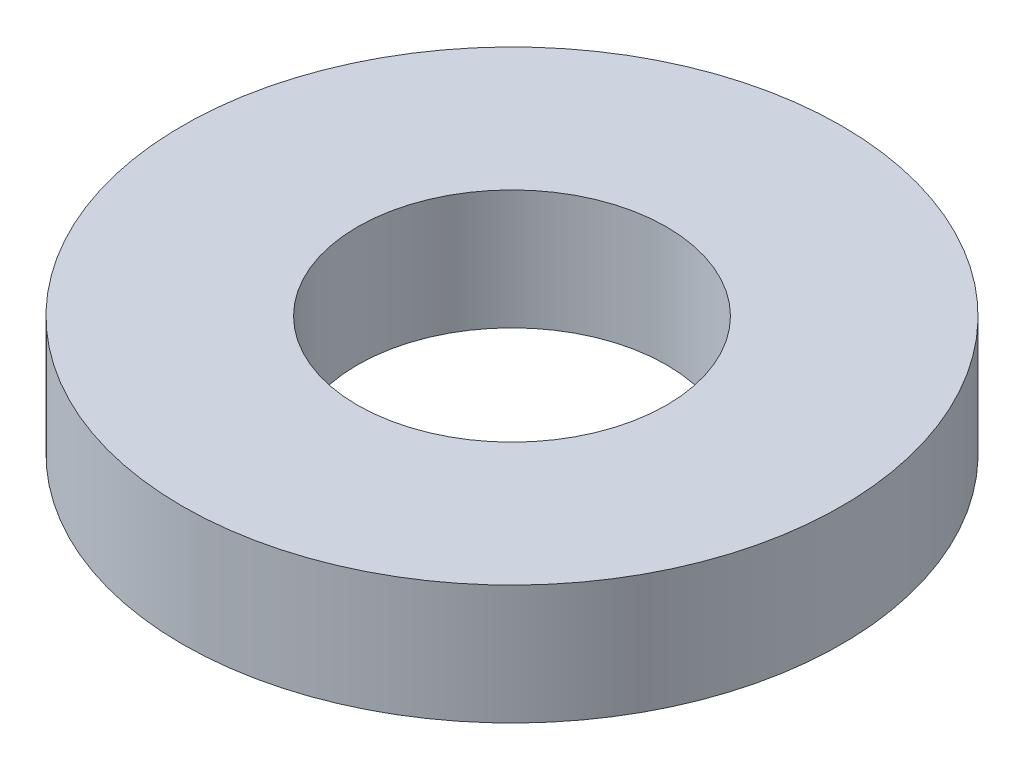
SolidWorks part; units mm, degrees
ref_plane "Front Plane" through (0, 0, 0) normal (0, 0, 1) x (1, 0, 0)
ref_plane "Top Plane" through (0, 0, 0) normal (0, 1, 0) x (1, 0, 0)
ref_plane "Right Plane" through (0, 0, 0) normal (1, 0, 0) x (0, 0, -1)
sketch "Sketch1" plane through (0, 0, 0) normal (0, 1, 0) x (1, 0, 0)
  circle A0 centre (0, 0) radius 80
  dimension "FLANGE_OD" = 160
extrude "Boss-Extrude1" add sketch "Sketch1" along normal blind 29
sketch "Sketch2" plane through (0, 0, 0) normal (0, 1, 0) x (1, 0, 0)
  circle A0 centre (0, 0) radius 37.5
  dimension "BORE_D" = 75
extrude "Cut-Extrude1" cut sketch "Sketch2" along normal through all
sketch "Sketch3" plane through (0, 29, 0) normal (0, 1, 0) x (1, 0, 0)
  circle A0 centre (0, 0) radius 35.2116 construction
  circle A1 centre (-35.2116, 0) radius 1.9371
  dimension "BOLT_D" = 3.8742
  dimension "BOLT_PCD" = 70.4232
extrude "Cut-Extrude2" cut sketch "Sketch3" against normal blind 25.1343 rebuild error yes
pattern_circular "CirPattern1" count 6 over 360 rebuild error yes
